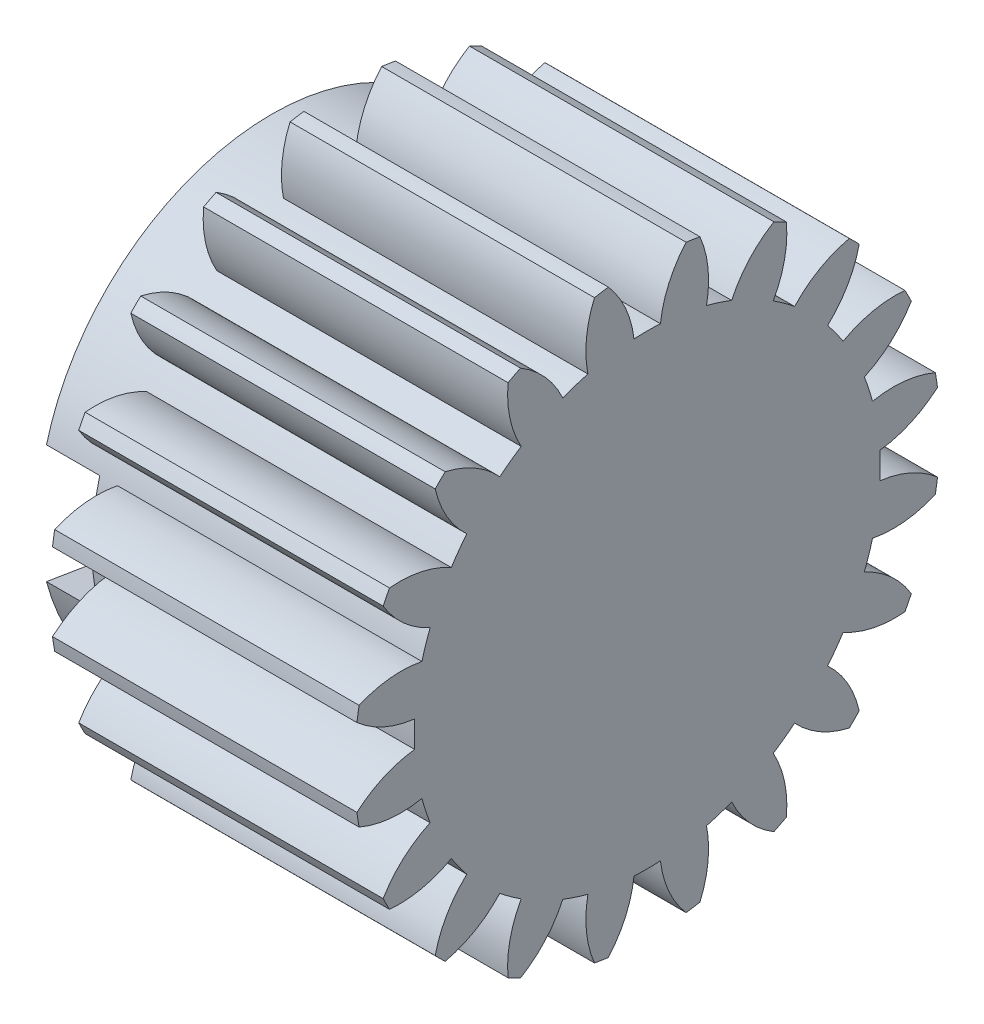
SolidWorks part; units mm, degrees
ref_plane "Plane1" through (0, 0, 0) normal (0, 0, 1) x (1, 0, 0)
ref_plane "Plane2" through (0, 0, 0) normal (0, 1, 0) x (1, 0, 0)
ref_plane "Plane3" through (0, 0, 0) normal (1, 0, 0) x (0, 0, -1)
other "Configuration Table"
sketch "HoldingSke" plane through (0, 0, 0) normal (0, 1, 0) x (1, 0, 0)
  line L0 (0, 0) -> (0.6265, -0.228)
  line L1 (-15, 0) -> (100, 0) construction
  line L2 (0, 0) -> (-2.1039, 2.3779)
  line L3 (0, 0) -> (-11.863, 4.5341)
  line L4 (0, 0) -> (8.1152, 2.9537)
  line L5 (0, 0) -> (-14.9912, -5.5913)
  line L6 (0, 0) -> (-8.2896, -5.593)
  line L7 (-2.1039, 2.3779) -> (1.3401, 18.0029)
  line L8 (-76.2, 54.61) -> (-76.1, 54.61)
  line L9 (-71.009, 38.7566) -> (-53.1078, 45.2721)
  line L10 (-76.2, 71.12) -> (104.1128, 71.12)
  line L11 (0, 0) -> (-10, 0)
  line L12 (-76.2, 101.6) -> (-76.147, 101.6)
  line L13 (24.9733, 27.94) -> (52.9518, 28.4284)
  line L14 (24.9733, 27.94) -> (24.9743, 27.94)
  line L15 (24.9733, 27.94) -> (100.4006, 29.5858)
  line L16 (-63.627, -1.5) -> (-12.827, -1.5)
  circle A0 centre (0, 0) radius 0.4
  circle A1 centre (0, 0) radius 13.124
  circle A2 centre (0, 0) radius 25
  circle A3 centre (0, 0) radius 0.4
  dimension "Num_teeth" = 20
  dimension "Pitch_radius" = 180.3128
  dimension "Width" = 10
  dimension "Thickness" = 10
sketch "BasProSke" plane through (0, 0, 0) normal (0, 1, 0) x (1, 0, 0)
  line L0 (-10, 0) -> (60, 0) construction
  line L1 (0, 0) -> (0, 16.5)
  line L2 (0, 0) -> (10, 0)
  line L3 (10, 0) -> (10, 16.5)
  line L4 (10, 16.5) -> (0, 16.5)
  dimension "Thickness" = 10
  dimension "Diameter" = 33
revolve "Base-Revolve" add sketch "BasProSke" angle 360 about L0
sketch "TooCutSke" plane through (0, 0, 0) normal (1, 0, 0) x (0, 0, -1)
  line L1 (0, 0) -> (0, 107) construction
  line L2 (0, 0) -> (-1.2696, 14.9462) construction
  line L3 (0, 0) -> (-4.6808, 29.5532) construction
  line L4 (-1.2696, 14.9462) -> (-2.3404, 14.7766) construction
  arc A0 (0.7438, 13.1029) -> (-0.7438, 13.1029) centre (0, 0) ccw
  arc A1 (2.21, 16.377) -> (-2.21, 16.377) centre (0, 0) ccw
  circle A2 centre (0, 0) radius 15 construction
  circle A3 centre (0, 0) radius 14.0954 construction
  arc A4 (-0.7438, 13.1029) -> (-2.21, 16.377) centre (-6.7025, 12.3999) ccw
  arc A5 (2.21, 16.377) -> (0.7438, 13.1029) centre (6.7025, 12.3999) ccw
extrude "ToothCut" cut sketch "TooCutSke" along normal through all
fillet "Breaks" [suppressed] radius 0.03 tangent propagation no
fillet "RootFillets" [suppressed] radius 0.376
pattern_circular "TeethCuts" count 20 every 18 about axis through (-10, 0, 0) along (1, 0, 0) of "ToothCut", "RootFillets", "Breaks"
sketch "HubNeaOneSke" plane through (0, 0, 0) normal (-1, 0, 0) x (0, 0, 1)
  circle A0 centre (0, 0) radius 13.124
  dimension "Diameter" = 26.248
extrude "HubNearOne" add sketch "HubNeaOneSke" along normal blind 6.0001
sketch "HubNeaBotSke" plane through (0, 0, 0) normal (-1, 0, 0) x (0, 0, 1)
  circle A0 centre (0, 0) radius 13.124
  dimension "Diameter" = 26.248
extrude "HubNearBoth" [suppressed] add sketch "HubNeaBotSke" along normal blind 3
ref_plane "FarPln" through (10, 0, 0) normal (1, 0, 0) x (0, 0, -1)
sketch "HubFarSke" plane through (10, 0, 0) normal (1, 0, 0) x (0, 0, -1)
  circle A0 centre (0, 0) radius 13.124
  dimension "Diameter" = 26.248
extrude "HubFar" [suppressed] add sketch "HubFarSke" along normal blind 3
sketch "BorSke" plane through (0, 0, 0) normal (1, 0, 0) x (0, 0, -1)
  circle A0 centre (0, 0) radius 0.4
  dimension "Diameter" = 0.8
extrude "Bore" cut sketch "BorSke" along normal mid plane 32.0001
sketch "KeySke" plane through (0, 0, 0) normal (1, 0, 0) x (0, 0, -1)
  line L0 (-0.05, 0) -> (-0.05, 0.5)
  line L1 (-0.05, 0.5) -> (0.05, 0.5)
  line L2 (0.05, 0.5) -> (0.05, 0)
  line L3 (0, 0) -> (0, 34) construction
  line L4 (-0.05, 0) -> (0.05, 0)
  dimension "Width" = 0.1
extrude "Keyway" [suppressed] cut sketch "KeySke" along normal mid plane 32.0001
pattern_circular "Keyway2" [suppressed] count 2 every 90 about axis through (-10, 0, 0) along (1, 0, 0) reverse direction yes
sketch "Sketch1" plane through (-6.0001, 0, 0) normal (-1, 0, 0) x (0, 0, 1)
  line L0 (0, 0) -> (31.5508, 0) construction
  line L1 (15.95, 2.8) -> (4.4173, 4.7)
  line L2 (15.95, -2.8) -> (4.4173, -4.7)
  line L3 (0, 10.0438) -> (0, -22.686) construction
  line L4 (-15.95, -2.8) -> (-4.4173, -4.7)
  line L5 (-15.95, 2.8) -> (-4.4173, 4.7)
  arc A0 (4.4173, 4.7) -> (-4.4173, 4.7) centre (0, 0) ccw
  circle A1 centre (0, 0) radius 4.25 construction
  arc A2 (15.95, -2.8) -> (15.95, 2.8) centre (15.95, 0) ccw
  arc A3 (-15.95, -2.8) -> (-15.95, 2.8) centre (-15.95, 0) cw
  arc A4 (-4.4173, -4.7) -> (4.4173, -4.7) centre (0, 0) ccw
  point P6 (4.25, 0)
  point P7 (18.75, 0)
  point P8 (4.4173, 4.7)
  point P9 (4.4173, -4.7)
  dimension "D1" = 8.5
  dimension "12.5" = 12.9
  dimension "D2" = 5.6
  dimension "D3" = 14.5
  dimension "D4" = 9.4
extrude "Cut-Extrude1" cut sketch "Sketch1" against normal blind 5
sketch "Sketch2" plane through (10, 0, 0) normal (1, 0, 0) x (0, 0, -1)
  arc A80 (-16.354, 2.1898) -> (-13.1029, 0.7438) centre (-12.3999, 6.7025) ccw
  arc A81 (-13.1029, 0.7438) -> (-13.1029, -0.7438) centre (0, 0) ccw
  arc A82 (-13.1029, -0.7438) -> (-16.354, -2.1898) centre (-12.3999, -6.7025) ccw
  arc A83 (-16.354, -2.1898) -> (-16.2303, -2.9711) centre (0, 0) ccw
  arc A84 (-16.2303, -2.9711) -> (-12.6915, -3.3416) centre (-13.8642, 2.5427) ccw
  arc A85 (-12.6915, -3.3416) -> (-12.2318, -4.7564) centre (0, 0) ccw
  arc A86 (-12.2318, -4.7564) -> (-14.8769, -7.1363) centre (-9.7218, -10.2062) ccw
  arc A87 (-14.8769, -7.1363) -> (-14.5178, -7.8411) centre (0, 0) ccw
  arc A88 (-14.5178, -7.8411) -> (-11.0377, -7.0999) centre (-13.9713, -1.866) ccw
  arc A89 (-11.0377, -7.0999) -> (-10.1633, -8.3035) centre (0, 0) ccw
  arc A90 (-10.1633, -8.3035) -> (-11.9436, -11.3842) centre (-6.0921, -12.7109) ccw
  arc A91 (-11.9436, -11.3842) -> (-11.3842, -11.9436) centre (0, 0) ccw
  arc A92 (-11.3842, -11.9436) -> (-8.3035, -10.1633) centre (-12.7109, -6.0921) ccw
  arc A93 (-8.3035, -10.1633) -> (-7.0999, -11.0377) centre (0, 0) ccw
  arc A94 (-7.0999, -11.0377) -> (-7.8411, -14.5178) centre (-1.866, -13.9713) ccw
  arc A95 (-7.8411, -14.5178) -> (-7.1363, -14.8769) centre (0, 0) ccw
  arc A96 (-7.1363, -14.8769) -> (-4.7564, -12.2318) centre (-10.2062, -9.7218) ccw
  arc A97 (-4.7564, -12.2318) -> (-3.3416, -12.6915) centre (0, 0) ccw
  arc A98 (-3.3416, -12.6915) -> (-2.9711, -16.2303) centre (2.5427, -13.8642) ccw
  arc A99 (-2.9711, -16.2303) -> (-2.1898, -16.354) centre (0, 0) ccw
  arc A100 (-2.1898, -16.354) -> (-0.7438, -13.1029) centre (-6.7025, -12.3999) ccw
  arc A101 (-0.7438, -13.1029) -> (0.7438, -13.1029) centre (0, 0) ccw
  arc A102 (0.7438, -13.1029) -> (2.1898, -16.354) centre (6.7025, -12.3999) ccw
  arc A103 (2.1898, -16.354) -> (2.9711, -16.2303) centre (0, 0) ccw
  arc A104 (2.9711, -16.2303) -> (3.3416, -12.6915) centre (-2.5427, -13.8642) ccw
  arc A105 (3.3416, -12.6915) -> (4.7564, -12.2318) centre (0, 0) ccw
  arc A106 (4.7564, -12.2318) -> (7.1363, -14.8769) centre (10.2062, -9.7218) ccw
  arc A107 (7.1363, -14.8769) -> (7.8411, -14.5178) centre (0, 0) ccw
  arc A108 (7.8411, -14.5178) -> (7.0999, -11.0377) centre (1.866, -13.9713) ccw
  arc A109 (7.0999, -11.0377) -> (8.3035, -10.1633) centre (0, 0) ccw
  arc A110 (8.3035, -10.1633) -> (11.3842, -11.9436) centre (12.7109, -6.0921) ccw
  arc A111 (11.3842, -11.9436) -> (11.9436, -11.3842) centre (0, 0) ccw
  arc A112 (11.9436, -11.3842) -> (10.1633, -8.3035) centre (6.0921, -12.7109) ccw
  arc A113 (10.1633, -8.3035) -> (11.0377, -7.0999) centre (0, 0) ccw
  arc A114 (11.0377, -7.0999) -> (14.5178, -7.8411) centre (13.9713, -1.866) ccw
  arc A115 (14.5178, -7.8411) -> (14.8769, -7.1363) centre (0, 0) ccw
  arc A116 (14.8769, -7.1363) -> (12.2318, -4.7564) centre (9.7218, -10.2062) ccw
  arc A117 (12.2318, -4.7564) -> (12.6915, -3.3416) centre (0, 0) ccw
  arc A118 (12.6915, -3.3416) -> (16.2303, -2.9711) centre (13.8642, 2.5427) ccw
  arc A119 (16.2303, -2.9711) -> (16.354, -2.1898) centre (0, 0) ccw
  arc A120 (16.354, -2.1898) -> (13.1029, -0.7438) centre (12.3999, -6.7025) ccw
  arc A121 (13.1029, -0.7438) -> (13.1029, 0.7438) centre (0, 0) ccw
  arc A122 (13.1029, 0.7438) -> (16.354, 2.1898) centre (12.3999, 6.7025) ccw
  arc A123 (16.354, 2.1898) -> (16.2303, 2.9711) centre (0, 0) ccw
  arc A124 (16.2303, 2.9711) -> (12.6915, 3.3416) centre (13.8642, -2.5427) ccw
  arc A125 (12.6915, 3.3416) -> (12.2318, 4.7564) centre (0, 0) ccw
  arc A126 (12.2318, 4.7564) -> (14.8769, 7.1363) centre (9.7218, 10.2062) ccw
  arc A127 (14.8769, 7.1363) -> (14.5178, 7.8411) centre (0, 0) ccw
  arc A128 (14.5178, 7.8411) -> (11.0377, 7.0999) centre (13.9713, 1.866) ccw
  arc A129 (11.0377, 7.0999) -> (10.1633, 8.3035) centre (0, 0) ccw
  arc A130 (10.1633, 8.3035) -> (11.9436, 11.3842) centre (6.0921, 12.7109) ccw
  arc A131 (11.9436, 11.3842) -> (11.3842, 11.9436) centre (0, 0) ccw
  arc A132 (11.3842, 11.9436) -> (8.3035, 10.1633) centre (12.7109, 6.0921) ccw
  arc A133 (8.3035, 10.1633) -> (7.0999, 11.0377) centre (0, 0) ccw
  arc A134 (7.0999, 11.0377) -> (7.8411, 14.5178) centre (1.866, 13.9713) ccw
  arc A135 (7.8411, 14.5178) -> (7.1363, 14.8769) centre (0, 0) ccw
  arc A136 (7.1363, 14.8769) -> (4.7564, 12.2318) centre (10.2062, 9.7218) ccw
  arc A137 (4.7564, 12.2318) -> (3.3416, 12.6915) centre (0, 0) ccw
  arc A138 (3.3416, 12.6915) -> (2.9711, 16.2303) centre (-2.5427, 13.8642) ccw
  arc A139 (2.9711, 16.2303) -> (2.1898, 16.354) centre (0, 0) ccw
  arc A140 (2.1898, 16.354) -> (0.7438, 13.1029) centre (6.7025, 12.3999) ccw
  arc A141 (0.7438, 13.1029) -> (-0.7438, 13.1029) centre (0, 0) ccw
  arc A142 (-0.7438, 13.1029) -> (-2.1898, 16.354) centre (-6.7025, 12.3999) ccw
  arc A143 (-2.1898, 16.354) -> (-2.9711, 16.2303) centre (0, 0) ccw
  arc A144 (-2.9711, 16.2303) -> (-3.3416, 12.6915) centre (2.5427, 13.8642) ccw
  arc A145 (-3.3416, 12.6915) -> (-4.7564, 12.2318) centre (0, 0) ccw
  arc A146 (-4.7564, 12.2318) -> (-7.1363, 14.8769) centre (-10.2062, 9.7218) ccw
  arc A147 (-7.1363, 14.8769) -> (-7.8411, 14.5178) centre (0, 0) ccw
  arc A148 (-7.8411, 14.5178) -> (-7.0999, 11.0377) centre (-1.866, 13.9713) ccw
  arc A149 (-7.0999, 11.0377) -> (-8.3035, 10.1633) centre (0, 0) ccw
  arc A150 (-8.3035, 10.1633) -> (-11.3842, 11.9436) centre (-12.7109, 6.0921) ccw
  arc A151 (-11.3842, 11.9436) -> (-11.9436, 11.3842) centre (0, 0) ccw
  arc A152 (-11.9436, 11.3842) -> (-10.1633, 8.3035) centre (-6.0921, 12.7109) ccw
  arc A153 (-10.1633, 8.3035) -> (-11.0377, 7.0999) centre (0, 0) ccw
  arc A154 (-11.0377, 7.0999) -> (-14.5178, 7.8411) centre (-13.9713, 1.866) ccw
  arc A155 (-14.5178, 7.8411) -> (-14.8769, 7.1363) centre (0, 0) ccw
  arc A156 (-14.8769, 7.1363) -> (-12.2318, 4.7564) centre (-9.7218, 10.2062) ccw
  arc A157 (-12.2318, 4.7564) -> (-12.6915, 3.3416) centre (0, 0) ccw
  arc A158 (-12.6915, 3.3416) -> (-16.2303, 2.9711) centre (-13.8642, -2.5427) ccw
  arc A159 (-16.2303, 2.9711) -> (-16.354, 2.1898) centre (0, 0) ccw
  arc A160 (-16.354, 2.1898) -> (-13.1029, 0.7438) centre (-12.3999, 6.7025) ccw
  arc A161 (-13.1029, 0.7438) -> (-13.1029, -0.7438) centre (0, 0) ccw
  arc A162 (-13.1029, -0.7438) -> (-16.354, -2.1898) centre (-12.3999, -6.7025) ccw
  arc A163 (-16.354, -2.1898) -> (-16.2303, -2.9711) centre (0, 0) ccw
  arc A164 (-16.2303, -2.9711) -> (-12.6915, -3.3416) centre (-13.8642, 2.5427) ccw
  arc A165 (-12.6915, -3.3416) -> (-12.2318, -4.7564) centre (0, 0) ccw
  arc A166 (-12.2318, -4.7564) -> (-14.8769, -7.1363) centre (-9.7218, -10.2062) ccw
  arc A167 (-14.8769, -7.1363) -> (-14.5178, -7.8411) centre (0, 0) ccw
  arc A168 (-14.5178, -7.8411) -> (-11.0377, -7.0999) centre (-13.9713, -1.866) ccw
  arc A169 (-11.0377, -7.0999) -> (-10.1633, -8.3035) centre (0, 0) ccw
  arc A170 (-10.1633, -8.3035) -> (-11.9436, -11.3842) centre (-6.0921, -12.7109) ccw
  arc A171 (-11.9436, -11.3842) -> (-11.3842, -11.9436) centre (0, 0) ccw
  arc A172 (-11.3842, -11.9436) -> (-8.3035, -10.1633) centre (-12.7109, -6.0921) ccw
  arc A173 (-8.3035, -10.1633) -> (-7.0999, -11.0377) centre (0, 0) ccw
  arc A174 (-7.0999, -11.0377) -> (-7.8411, -14.5178) centre (-1.866, -13.9713) ccw
  arc A175 (-7.8411, -14.5178) -> (-7.1363, -14.8769) centre (0, 0) ccw
  arc A176 (-7.1363, -14.8769) -> (-4.7564, -12.2318) centre (-10.2062, -9.7218) ccw
  arc A177 (-4.7564, -12.2318) -> (-3.3416, -12.6915) centre (0, 0) ccw
  arc A178 (-3.3416, -12.6915) -> (-2.9711, -16.2303) centre (2.5427, -13.8642) ccw
  arc A179 (-2.9711, -16.2303) -> (-2.1898, -16.354) centre (0, 0) ccw
  arc A180 (-2.1898, -16.354) -> (-0.7438, -13.1029) centre (-6.7025, -12.3999) ccw
  arc A181 (-0.7438, -13.1029) -> (0.7438, -13.1029) centre (0, 0) ccw
  arc A182 (0.7438, -13.1029) -> (2.1898, -16.354) centre (6.7025, -12.3999) ccw
  arc A183 (2.1898, -16.354) -> (2.9711, -16.2303) centre (0, 0) ccw
  arc A184 (2.9711, -16.2303) -> (3.3416, -12.6915) centre (-2.5427, -13.8642) ccw
  arc A185 (3.3416, -12.6915) -> (4.7564, -12.2318) centre (0, 0) ccw
  arc A186 (4.7564, -12.2318) -> (7.1363, -14.8769) centre (10.2062, -9.7218) ccw
  arc A187 (7.1363, -14.8769) -> (7.8411, -14.5178) centre (0, 0) ccw
  arc A188 (7.8411, -14.5178) -> (7.0999, -11.0377) centre (1.866, -13.9713) ccw
  arc A189 (7.0999, -11.0377) -> (8.3035, -10.1633) centre (0, 0) ccw
  arc A190 (8.3035, -10.1633) -> (11.3842, -11.9436) centre (12.7109, -6.0921) ccw
  arc A191 (11.3842, -11.9436) -> (11.9436, -11.3842) centre (0, 0) ccw
  arc A192 (11.9436, -11.3842) -> (10.1633, -8.3035) centre (6.0921, -12.7109) ccw
  arc A193 (10.1633, -8.3035) -> (11.0377, -7.0999) centre (0, 0) ccw
  arc A194 (11.0377, -7.0999) -> (14.5178, -7.8411) centre (13.9713, -1.866) ccw
  arc A195 (14.5178, -7.8411) -> (14.8769, -7.1363) centre (0, 0) ccw
  arc A196 (14.8769, -7.1363) -> (12.2318, -4.7564) centre (9.7218, -10.2062) ccw
  arc A197 (12.2318, -4.7564) -> (12.6915, -3.3416) centre (0, 0) ccw
  arc A198 (12.6915, -3.3416) -> (16.2303, -2.9711) centre (13.8642, 2.5427) ccw
  arc A199 (16.2303, -2.9711) -> (16.354, -2.1898) centre (0, 0) ccw
  arc A200 (16.354, -2.1898) -> (13.1029, -0.7438) centre (12.3999, -6.7025) ccw
  arc A201 (13.1029, -0.7438) -> (13.1029, 0.7438) centre (0, 0) ccw
  arc A202 (13.1029, 0.7438) -> (16.354, 2.1898) centre (12.3999, 6.7025) ccw
  arc A203 (16.354, 2.1898) -> (16.2303, 2.9711) centre (0, 0) ccw
  arc A204 (16.2303, 2.9711) -> (12.6915, 3.3416) centre (13.8642, -2.5427) ccw
  arc A205 (12.6915, 3.3416) -> (12.2318, 4.7564) centre (0, 0) ccw
  arc A206 (12.2318, 4.7564) -> (14.8769, 7.1363) centre (9.7218, 10.2062) ccw
  arc A207 (14.8769, 7.1363) -> (14.5178, 7.8411) centre (0, 0) ccw
  arc A208 (14.5178, 7.8411) -> (11.0377, 7.0999) centre (13.9713, 1.866) ccw
  arc A209 (11.0377, 7.0999) -> (10.1633, 8.3035) centre (0, 0) ccw
  arc A210 (10.1633, 8.3035) -> (11.9436, 11.3842) centre (6.0921, 12.7109) ccw
  arc A211 (11.9436, 11.3842) -> (11.3842, 11.9436) centre (0, 0) ccw
  arc A212 (11.3842, 11.9436) -> (8.3035, 10.1633) centre (12.7109, 6.0921) ccw
  arc A213 (8.3035, 10.1633) -> (7.0999, 11.0377) centre (0, 0) ccw
  arc A214 (7.0999, 11.0377) -> (7.8411, 14.5178) centre (1.866, 13.9713) ccw
  arc A215 (7.8411, 14.5178) -> (7.1363, 14.8769) centre (0, 0) ccw
  arc A216 (7.1363, 14.8769) -> (4.7564, 12.2318) centre (10.2062, 9.7218) ccw
  arc A217 (4.7564, 12.2318) -> (3.3416, 12.6915) centre (0, 0) ccw
  arc A218 (3.3416, 12.6915) -> (2.9711, 16.2303) centre (-2.5427, 13.8642) ccw
  arc A219 (2.9711, 16.2303) -> (2.1898, 16.354) centre (0, 0) ccw
  arc A220 (2.1898, 16.354) -> (0.7438, 13.1029) centre (6.7025, 12.3999) ccw
  arc A221 (0.7438, 13.1029) -> (-0.7438, 13.1029) centre (0, 0) ccw
  arc A222 (-0.7438, 13.1029) -> (-2.1898, 16.354) centre (-6.7025, 12.3999) ccw
  arc A223 (-2.1898, 16.354) -> (-2.9711, 16.2303) centre (0, 0) ccw
  arc A224 (-2.9711, 16.2303) -> (-3.3416, 12.6915) centre (2.5427, 13.8642) ccw
  arc A225 (-3.3416, 12.6915) -> (-4.7564, 12.2318) centre (0, 0) ccw
  arc A226 (-4.7564, 12.2318) -> (-7.1363, 14.8769) centre (-10.2062, 9.7218) ccw
  arc A227 (-7.1363, 14.8769) -> (-7.8411, 14.5178) centre (0, 0) ccw
  arc A228 (-7.8411, 14.5178) -> (-7.0999, 11.0377) centre (-1.866, 13.9713) ccw
  arc A229 (-7.0999, 11.0377) -> (-8.3035, 10.1633) centre (0, 0) ccw
  arc A230 (-8.3035, 10.1633) -> (-11.3842, 11.9436) centre (-12.7109, 6.0921) ccw
  arc A231 (-11.3842, 11.9436) -> (-11.9436, 11.3842) centre (0, 0) ccw
  arc A232 (-11.9436, 11.3842) -> (-10.1633, 8.3035) centre (-6.0921, 12.7109) ccw
  arc A233 (-10.1633, 8.3035) -> (-11.0377, 7.0999) centre (0, 0) ccw
  arc A234 (-11.0377, 7.0999) -> (-14.5178, 7.8411) centre (-13.9713, 1.866) ccw
  arc A235 (-14.5178, 7.8411) -> (-14.8769, 7.1363) centre (0, 0) ccw
  arc A236 (-14.8769, 7.1363) -> (-12.2318, 4.7564) centre (-9.7218, 10.2062) ccw
  arc A237 (-12.2318, 4.7564) -> (-12.6915, 3.3416) centre (0, 0) ccw
  arc A238 (-12.6915, 3.3416) -> (-16.2303, 2.9711) centre (-13.8642, -2.5427) ccw
  arc A239 (-16.2303, 2.9711) -> (-16.354, 2.1898) centre (0, 0) ccw
  dimension "D1" = 0
extrude "Boss-Extrude1" add sketch "Sketch2" along normal blind 7.15 contours A160 A161 A162 A163 A164 A165 A166 A167 A168 A169 A170 A171 A172 A173 A174 A175 A176 A177 A178 A179 A180 A181 A182 A183 A184 A185 A186 A187 A188 A189 A190 A191 A192 A193 A194 A195 A196 A197 A198 A199 A200 A201 A202 A203 A204 A205 A206 A207 A208 A209 A210 A211 A212 A213 A214 A215 A216 A217 A218 A219 A220 A221 A222 A223 A224 A225 A226 A227 A228 A229 A230 A231 A232 A233 A234 A235 A236 A237 A238 A239
sketch "Sketch4" plane through (-6.0001, 0, 0) normal (-1, 0, 0) x (0, 0, 1)
  circle A0 centre (0, 0) radius 13.124
extrude "Cut-Extrude2" cut sketch "Sketch4" against normal blind 2
sketch "Sketch5" plane through (17.15, 0, 0) normal (1, 0, 0) x (0, 0, -1)
  arc A80 (-16.2303, 2.9711) -> (-16.354, 2.1898) centre (0, 0) ccw
  arc A81 (-16.354, 2.1898) -> (-13.1029, 0.7438) centre (-12.3999, 6.7025) ccw
  arc A82 (-13.1029, 0.7438) -> (-13.1029, -0.7438) centre (0, 0) ccw
  arc A83 (-13.1029, -0.7438) -> (-16.354, -2.1898) centre (-12.3999, -6.7025) ccw
  arc A84 (-16.354, -2.1898) -> (-16.2303, -2.9711) centre (0, 0) ccw
  arc A85 (-16.2303, -2.9711) -> (-12.6915, -3.3416) centre (-13.8642, 2.5427) ccw
  arc A86 (-12.6915, -3.3416) -> (-12.2318, -4.7564) centre (0, 0) ccw
  arc A87 (-12.2318, -4.7564) -> (-14.8769, -7.1363) centre (-9.7218, -10.2062) ccw
  arc A88 (-14.8769, -7.1363) -> (-14.5178, -7.8411) centre (0, 0) ccw
  arc A89 (-14.5178, -7.8411) -> (-11.0377, -7.0999) centre (-13.9713, -1.866) ccw
  arc A90 (-11.0377, -7.0999) -> (-10.1633, -8.3035) centre (0, 0) ccw
  arc A91 (-10.1633, -8.3035) -> (-11.9436, -11.3842) centre (-6.0921, -12.7109) ccw
  arc A92 (-11.9436, -11.3842) -> (-11.3842, -11.9436) centre (0, 0) ccw
  arc A93 (-11.3842, -11.9436) -> (-8.3035, -10.1633) centre (-12.7109, -6.0921) ccw
  arc A94 (-8.3035, -10.1633) -> (-7.0999, -11.0377) centre (0, 0) ccw
  arc A95 (-7.0999, -11.0377) -> (-7.8411, -14.5178) centre (-1.866, -13.9713) ccw
  arc A96 (-7.8411, -14.5178) -> (-7.1363, -14.8769) centre (0, 0) ccw
  arc A97 (-7.1363, -14.8769) -> (-4.7564, -12.2318) centre (-10.2062, -9.7218) ccw
  arc A98 (-4.7564, -12.2318) -> (-3.3416, -12.6915) centre (0, 0) ccw
  arc A99 (-3.3416, -12.6915) -> (-2.9711, -16.2303) centre (2.5427, -13.8642) ccw
  arc A100 (-2.9711, -16.2303) -> (-2.1898, -16.354) centre (0, 0) ccw
  arc A101 (-2.1898, -16.354) -> (-0.7438, -13.1029) centre (-6.7025, -12.3999) ccw
  arc A102 (-0.7438, -13.1029) -> (0.7438, -13.1029) centre (0, 0) ccw
  arc A103 (0.7438, -13.1029) -> (2.1898, -16.354) centre (6.7025, -12.3999) ccw
  arc A104 (2.1898, -16.354) -> (2.9711, -16.2303) centre (0, 0) ccw
  arc A105 (2.9711, -16.2303) -> (3.3416, -12.6915) centre (-2.5427, -13.8642) ccw
  arc A106 (3.3416, -12.6915) -> (4.7564, -12.2318) centre (0, 0) ccw
  arc A107 (4.7564, -12.2318) -> (7.1363, -14.8769) centre (10.2062, -9.7218) ccw
  arc A108 (7.1363, -14.8769) -> (7.8411, -14.5178) centre (0, 0) ccw
  arc A109 (7.8411, -14.5178) -> (7.0999, -11.0377) centre (1.866, -13.9713) ccw
  arc A110 (7.0999, -11.0377) -> (8.3035, -10.1633) centre (0, 0) ccw
  arc A111 (8.3035, -10.1633) -> (11.3842, -11.9436) centre (12.7109, -6.0921) ccw
  arc A112 (11.3842, -11.9436) -> (11.9436, -11.3842) centre (0, 0) ccw
  arc A113 (11.9436, -11.3842) -> (10.1633, -8.3035) centre (6.0921, -12.7109) ccw
  arc A114 (10.1633, -8.3035) -> (11.0377, -7.0999) centre (0, 0) ccw
  arc A115 (11.0377, -7.0999) -> (14.5178, -7.8411) centre (13.9713, -1.866) ccw
  arc A116 (14.5178, -7.8411) -> (14.8769, -7.1363) centre (0, 0) ccw
  arc A117 (14.8769, -7.1363) -> (12.2318, -4.7564) centre (9.7218, -10.2062) ccw
  arc A118 (12.2318, -4.7564) -> (12.6915, -3.3416) centre (0, 0) ccw
  arc A119 (12.6915, -3.3416) -> (16.2303, -2.9711) centre (13.8642, 2.5427) ccw
  arc A120 (16.2303, -2.9711) -> (16.354, -2.1898) centre (0, 0) ccw
  arc A121 (16.354, -2.1898) -> (13.1029, -0.7438) centre (12.3999, -6.7025) ccw
  arc A122 (13.1029, -0.7438) -> (13.1029, 0.7438) centre (0, 0) ccw
  arc A123 (13.1029, 0.7438) -> (16.354, 2.1898) centre (12.3999, 6.7025) ccw
  arc A124 (16.354, 2.1898) -> (16.2303, 2.9711) centre (0, 0) ccw
  arc A125 (16.2303, 2.9711) -> (12.6915, 3.3416) centre (13.8642, -2.5427) ccw
  arc A126 (12.6915, 3.3416) -> (12.2318, 4.7564) centre (0, 0) ccw
  arc A127 (12.2318, 4.7564) -> (14.8769, 7.1363) centre (9.7218, 10.2062) ccw
  arc A128 (14.8769, 7.1363) -> (14.5178, 7.8411) centre (0, 0) ccw
  arc A129 (14.5178, 7.8411) -> (11.0377, 7.0999) centre (13.9713, 1.866) ccw
  arc A130 (11.0377, 7.0999) -> (10.1633, 8.3035) centre (0, 0) ccw
  arc A131 (10.1633, 8.3035) -> (11.9436, 11.3842) centre (6.0921, 12.7109) ccw
  arc A132 (11.9436, 11.3842) -> (11.3842, 11.9436) centre (0, 0) ccw
  arc A133 (11.3842, 11.9436) -> (8.3035, 10.1633) centre (12.7109, 6.0921) ccw
  arc A134 (8.3035, 10.1633) -> (7.0999, 11.0377) centre (0, 0) ccw
  arc A135 (7.0999, 11.0377) -> (7.8411, 14.5178) centre (1.866, 13.9713) ccw
  arc A136 (7.8411, 14.5178) -> (7.1363, 14.8769) centre (0, 0) ccw
  arc A137 (7.1363, 14.8769) -> (4.7564, 12.2318) centre (10.2062, 9.7218) ccw
  arc A138 (4.7564, 12.2318) -> (3.3416, 12.6915) centre (0, 0) ccw
  arc A139 (3.3416, 12.6915) -> (2.9711, 16.2303) centre (-2.5427, 13.8642) ccw
  arc A140 (2.9711, 16.2303) -> (2.1898, 16.354) centre (0, 0) ccw
  arc A141 (2.1898, 16.354) -> (0.7438, 13.1029) centre (6.7025, 12.3999) ccw
  arc A142 (0.7438, 13.1029) -> (-0.7438, 13.1029) centre (0, 0) ccw
  arc A143 (-0.7438, 13.1029) -> (-2.1898, 16.354) centre (-6.7025, 12.3999) ccw
  arc A144 (-2.1898, 16.354) -> (-2.9711, 16.2303) centre (0, 0) ccw
  arc A145 (-2.9711, 16.2303) -> (-3.3416, 12.6915) centre (2.5427, 13.8642) ccw
  arc A146 (-3.3416, 12.6915) -> (-4.7564, 12.2318) centre (0, 0) ccw
  arc A147 (-4.7564, 12.2318) -> (-7.1363, 14.8769) centre (-10.2062, 9.7218) ccw
  arc A148 (-7.1363, 14.8769) -> (-7.8411, 14.5178) centre (0, 0) ccw
  arc A149 (-7.8411, 14.5178) -> (-7.0999, 11.0377) centre (-1.866, 13.9713) ccw
  arc A150 (-7.0999, 11.0377) -> (-8.3035, 10.1633) centre (0, 0) ccw
  arc A151 (-8.3035, 10.1633) -> (-11.3842, 11.9436) centre (-12.7109, 6.0921) ccw
  arc A152 (-11.3842, 11.9436) -> (-11.9436, 11.3842) centre (0, 0) ccw
  arc A153 (-11.9436, 11.3842) -> (-10.1633, 8.3035) centre (-6.0921, 12.7109) ccw
  arc A154 (-10.1633, 8.3035) -> (-11.0377, 7.0999) centre (0, 0) ccw
  arc A155 (-11.0377, 7.0999) -> (-14.5178, 7.8411) centre (-13.9713, 1.866) ccw
  arc A156 (-14.5178, 7.8411) -> (-14.8769, 7.1363) centre (0, 0) ccw
  arc A157 (-14.8769, 7.1363) -> (-12.2318, 4.7564) centre (-9.7218, 10.2062) ccw
  arc A158 (-12.2318, 4.7564) -> (-12.6915, 3.3416) centre (0, 0) ccw
  arc A159 (-12.6915, 3.3416) -> (-16.2303, 2.9711) centre (-13.8642, -2.5427) ccw
  arc A160 (-16.2303, 2.9711) -> (-16.354, 2.1898) centre (0, 0) ccw
  arc A161 (-16.354, 2.1898) -> (-13.1029, 0.7438) centre (-12.3999, 6.7025) ccw
  arc A162 (-13.1029, 0.7438) -> (-13.1029, -0.7438) centre (0, 0) ccw
  arc A163 (-13.1029, -0.7438) -> (-16.354, -2.1898) centre (-12.3999, -6.7025) ccw
  arc A164 (-16.354, -2.1898) -> (-16.2303, -2.9711) centre (0, 0) ccw
  arc A165 (-16.2303, -2.9711) -> (-12.6915, -3.3416) centre (-13.8642, 2.5427) ccw
  arc A166 (-12.6915, -3.3416) -> (-12.2318, -4.7564) centre (0, 0) ccw
  arc A167 (-12.2318, -4.7564) -> (-14.8769, -7.1363) centre (-9.7218, -10.2062) ccw
  arc A168 (-14.8769, -7.1363) -> (-14.5178, -7.8411) centre (0, 0) ccw
  arc A169 (-14.5178, -7.8411) -> (-11.0377, -7.0999) centre (-13.9713, -1.866) ccw
  arc A170 (-11.0377, -7.0999) -> (-10.1633, -8.3035) centre (0, 0) ccw
  arc A171 (-10.1633, -8.3035) -> (-11.9436, -11.3842) centre (-6.0921, -12.7109) ccw
  arc A172 (-11.9436, -11.3842) -> (-11.3842, -11.9436) centre (0, 0) ccw
  arc A173 (-11.3842, -11.9436) -> (-8.3035, -10.1633) centre (-12.7109, -6.0921) ccw
  arc A174 (-8.3035, -10.1633) -> (-7.0999, -11.0377) centre (0, 0) ccw
  arc A175 (-7.0999, -11.0377) -> (-7.8411, -14.5178) centre (-1.866, -13.9713) ccw
  arc A176 (-7.8411, -14.5178) -> (-7.1363, -14.8769) centre (0, 0) ccw
  arc A177 (-7.1363, -14.8769) -> (-4.7564, -12.2318) centre (-10.2062, -9.7218) ccw
  arc A178 (-4.7564, -12.2318) -> (-3.3416, -12.6915) centre (0, 0) ccw
  arc A179 (-3.3416, -12.6915) -> (-2.9711, -16.2303) centre (2.5427, -13.8642) ccw
  arc A180 (-2.9711, -16.2303) -> (-2.1898, -16.354) centre (0, 0) ccw
  arc A181 (-2.1898, -16.354) -> (-0.7438, -13.1029) centre (-6.7025, -12.3999) ccw
  arc A182 (-0.7438, -13.1029) -> (0.7438, -13.1029) centre (0, 0) ccw
  arc A183 (0.7438, -13.1029) -> (2.1898, -16.354) centre (6.7025, -12.3999) ccw
  arc A184 (2.1898, -16.354) -> (2.9711, -16.2303) centre (0, 0) ccw
  arc A185 (2.9711, -16.2303) -> (3.3416, -12.6915) centre (-2.5427, -13.8642) ccw
  arc A186 (3.3416, -12.6915) -> (4.7564, -12.2318) centre (0, 0) ccw
  arc A187 (4.7564, -12.2318) -> (7.1363, -14.8769) centre (10.2062, -9.7218) ccw
  arc A188 (7.1363, -14.8769) -> (7.8411, -14.5178) centre (0, 0) ccw
  arc A189 (7.8411, -14.5178) -> (7.0999, -11.0377) centre (1.866, -13.9713) ccw
  arc A190 (7.0999, -11.0377) -> (8.3035, -10.1633) centre (0, 0) ccw
  arc A191 (8.3035, -10.1633) -> (11.3842, -11.9436) centre (12.7109, -6.0921) ccw
  arc A192 (11.3842, -11.9436) -> (11.9436, -11.3842) centre (0, 0) ccw
  arc A193 (11.9436, -11.3842) -> (10.1633, -8.3035) centre (6.0921, -12.7109) ccw
  arc A194 (10.1633, -8.3035) -> (11.0377, -7.0999) centre (0, 0) ccw
  arc A195 (11.0377, -7.0999) -> (14.5178, -7.8411) centre (13.9713, -1.866) ccw
  arc A196 (14.5178, -7.8411) -> (14.8769, -7.1363) centre (0, 0) ccw
  arc A197 (14.8769, -7.1363) -> (12.2318, -4.7564) centre (9.7218, -10.2062) ccw
  arc A198 (12.2318, -4.7564) -> (12.6915, -3.3416) centre (0, 0) ccw
  arc A199 (12.6915, -3.3416) -> (16.2303, -2.9711) centre (13.8642, 2.5427) ccw
  arc A200 (16.2303, -2.9711) -> (16.354, -2.1898) centre (0, 0) ccw
  arc A201 (16.354, -2.1898) -> (13.1029, -0.7438) centre (12.3999, -6.7025) ccw
  arc A202 (13.1029, -0.7438) -> (13.1029, 0.7438) centre (0, 0) ccw
  arc A203 (13.1029, 0.7438) -> (16.354, 2.1898) centre (12.3999, 6.7025) ccw
  arc A204 (16.354, 2.1898) -> (16.2303, 2.9711) centre (0, 0) ccw
  arc A205 (16.2303, 2.9711) -> (12.6915, 3.3416) centre (13.8642, -2.5427) ccw
  arc A206 (12.6915, 3.3416) -> (12.2318, 4.7564) centre (0, 0) ccw
  arc A207 (12.2318, 4.7564) -> (14.8769, 7.1363) centre (9.7218, 10.2062) ccw
  arc A208 (14.8769, 7.1363) -> (14.5178, 7.8411) centre (0, 0) ccw
  arc A209 (14.5178, 7.8411) -> (11.0377, 7.0999) centre (13.9713, 1.866) ccw
  arc A210 (11.0377, 7.0999) -> (10.1633, 8.3035) centre (0, 0) ccw
  arc A211 (10.1633, 8.3035) -> (11.9436, 11.3842) centre (6.0921, 12.7109) ccw
  arc A212 (11.9436, 11.3842) -> (11.3842, 11.9436) centre (0, 0) ccw
  arc A213 (11.3842, 11.9436) -> (8.3035, 10.1633) centre (12.7109, 6.0921) ccw
  arc A214 (8.3035, 10.1633) -> (7.0999, 11.0377) centre (0, 0) ccw
  arc A215 (7.0999, 11.0377) -> (7.8411, 14.5178) centre (1.866, 13.9713) ccw
  arc A216 (7.8411, 14.5178) -> (7.1363, 14.8769) centre (0, 0) ccw
  arc A217 (7.1363, 14.8769) -> (4.7564, 12.2318) centre (10.2062, 9.7218) ccw
  arc A218 (4.7564, 12.2318) -> (3.3416, 12.6915) centre (0, 0) ccw
  arc A219 (3.3416, 12.6915) -> (2.9711, 16.2303) centre (-2.5427, 13.8642) ccw
  arc A220 (2.9711, 16.2303) -> (2.1898, 16.354) centre (0, 0) ccw
  arc A221 (2.1898, 16.354) -> (0.7438, 13.1029) centre (6.7025, 12.3999) ccw
  arc A222 (0.7438, 13.1029) -> (-0.7438, 13.1029) centre (0, 0) ccw
  arc A223 (-0.7438, 13.1029) -> (-2.1898, 16.354) centre (-6.7025, 12.3999) ccw
  arc A224 (-2.1898, 16.354) -> (-2.9711, 16.2303) centre (0, 0) ccw
  arc A225 (-2.9711, 16.2303) -> (-3.3416, 12.6915) centre (2.5427, 13.8642) ccw
  arc A226 (-3.3416, 12.6915) -> (-4.7564, 12.2318) centre (0, 0) ccw
  arc A227 (-4.7564, 12.2318) -> (-7.1363, 14.8769) centre (-10.2062, 9.7218) ccw
  arc A228 (-7.1363, 14.8769) -> (-7.8411, 14.5178) centre (0, 0) ccw
  arc A229 (-7.8411, 14.5178) -> (-7.0999, 11.0377) centre (-1.866, 13.9713) ccw
  arc A230 (-7.0999, 11.0377) -> (-8.3035, 10.1633) centre (0, 0) ccw
  arc A231 (-8.3035, 10.1633) -> (-11.3842, 11.9436) centre (-12.7109, 6.0921) ccw
  arc A232 (-11.3842, 11.9436) -> (-11.9436, 11.3842) centre (0, 0) ccw
  arc A233 (-11.9436, 11.3842) -> (-10.1633, 8.3035) centre (-6.0921, 12.7109) ccw
  arc A234 (-10.1633, 8.3035) -> (-11.0377, 7.0999) centre (0, 0) ccw
  arc A235 (-11.0377, 7.0999) -> (-14.5178, 7.8411) centre (-13.9713, 1.866) ccw
  arc A236 (-14.5178, 7.8411) -> (-14.8769, 7.1363) centre (0, 0) ccw
  arc A237 (-14.8769, 7.1363) -> (-12.2318, 4.7564) centre (-9.7218, 10.2062) ccw
  arc A238 (-12.2318, 4.7564) -> (-12.6915, 3.3416) centre (0, 0) ccw
  arc A239 (-12.6915, 3.3416) -> (-16.2303, 2.9711) centre (-13.8642, -2.5427) ccw
  dimension "D1" = 0
equation "' \"Module@HoldingSke\" = 6.35"
equation "' \"Num_teeth@HoldingSke\" = 12"
equation "' \"Ap@HoldingSke\" =  20"
equation "' \"Ap@HoldingSke\" = 20"
equation "' \"Width@HoldingSke\" = 0.5 * 25.4"
equation "' \"Hub_dia@HoldingSke\"= 1 * 25.4"
equation "' \"Hub_dia@HoldingSke\" = 1 * 25.4"
equation "' \"Overall_len@HoldingSke\" = 1.0 * 25.4"
equation "' \"Bore@HoldingSke\" = 0.75 * 25.4"
equation "' \"T_dim@HoldingSke\" = 0.1 * 25.4"
equation "' \"Width@KeySke\" = 0.25 * 25.4"
equation "' \"Show_teeth@HoldingSke\" = 13"
equation "' \"Backlash@HoldingSke\" = 0.009 * 25.4"
equation "' \"Addendum_fac@HoldingSke\" = 1.0"
equation "' \"Dedendum_fac@HoldingSke\" = 1.25"
equation "' \"Dedendum_add@HoldingSke\" = 0.00005 * 25.4"
equation "' \"Clearance_fac@HoldingSke\" = 0.25"
equation "\"Pitch@HoldingSke\" = 1 / \"Module@HoldingSke\""
equation "\"Overcut_dia@TooCutSke\" = (\"Num_teeth@HoldingSke\" + 2 * \"Addendum_fac@HoldingSke\") / \"Pitch@HoldingSke\" + 0.002 * 25.4"
equation "\"Pitch_dia@TooCutSke\" = \"Num_teeth@HoldingSke\" / \"Pitch@HoldingSke\""
equation "\"Base_dia@TooCutSke\" = \"Num_teeth@HoldingSke\" / \"Pitch@HoldingSke\" * cos((\"Ap@HoldingSke\"  * 3.14159265 / 180))"
equation "\"Root_dia@TooCutSke\" = (\"Num_teeth@HoldingSke\" + 2) / \"Pitch@HoldingSke\" - 2 * (\"Addendum_fac@HoldingSke\" + \"Dedendum_fac@HoldingSke\") / \"Pitch@HoldingSke\" - \"Dedendum_add@HoldingSke\" * 2"
equation "\"Half_ang@TooCutSke\" = 180 / \"Num_teeth@HoldingSke\""
equation "\"Half_CT@TooCutSke\" = \"Num_teeth@HoldingSke\" / \"Pitch@HoldingSke\" * sin((3.14159265 / 2 / \"Num_teeth@HoldingSke\")) / 2 - 7 * \"Backlash@HoldingSke\" / 4"
equation "\"Flank_rad@TooCutSke\" = \"Num_teeth@HoldingSke\" / \"Pitch@HoldingSke\" / 5"
equation "\"Radius@RootFillets\" = \"Clearance_fac@HoldingSke\" / \"Pitch@HoldingSke\" + \"Dedendum_add@HoldingSke\""
equation "\"Break_rad@Breaks\" = 0.02 / \"Pitch@HoldingSke\""
equation "\"Thickness@HoldingSke\" = \"Width@HoldingSke\""
equation "\"OAL@HoldingSke\" = \"Thickness@HoldingSke\""
equation "\"MHD@HoldingSke\" = (\"Num_teeth@HoldingSke\" + 2) / \"Pitch@HoldingSke\" - 2 * (\"Addendum_fac@HoldingSke\" + \"Dedendum_fac@HoldingSke\")  / \"Pitch@HoldingSke\" - \"Dedendum_add@HoldingSke\" * 2"
equation "\"MBD@HoldingSke\" = (\"Num_teeth@HoldingSke\" + 2) / \"Pitch@HoldingSke\" - 2 * (\"Addendum_fac@HoldingSke\" + \"Dedendum_fac@HoldingSke\")  / \"Pitch@HoldingSke\" - \"Dedendum_add@HoldingSke\" * 2 - 0.002 * 25.4"
equation "\"MHD@HoldingSke\" = ((sgn( \"MHD@HoldingSke\" - \"Hub_dia@HoldingSke\" )-1)*( \"MHD@HoldingSke\" - \"Hub_dia@HoldingSke\" ))/-2+ \"Hub_dia@HoldingSke\""
equation "\"MBD@HoldingSke\" = ((sgn( \"MBD@HoldingSke\" - \"Bore@HoldingSke\" )-1)*( \"MBD@HoldingSke\" - \"Bore@HoldingSke\" ))/-2+ \"Bore@HoldingSke\""
equation "\"OAL@HoldingSke\" = ((sgn( \"OAL@HoldingSke\" - \"Overall_len@HoldingSke\" )+1)*( \"OAL@HoldingSke\" - \"Overall_len@HoldingSke\" ))/2 + \"Overall_len@HoldingSke\" + 0.000002 * 25.4"
equation "\"Num_teeth@TeethCuts\" = int( \"Show_teeth@HoldingSke\" ) + 1"
equation "\"Num_teeth@TeethCuts\" = ((sgn( \"Num_teeth@TeethCuts\" - \"Num_teeth@HoldingSke\" )-1)*( \"Num_teeth@TeethCuts\" - \"Num_teeth@HoldingSke\" ))/-2+ \"Num_teeth@HoldingSke\""
equation "\"Num_teeth@TeethCuts\" = ((sgn( \"Num_teeth@TeethCuts\" - 2.0)+1)*( \"Num_teeth@TeethCuts\" - 2.0))/2 +2.0"
equation "\"Angle@TeethCuts\" = 360.0 / \"Num_teeth@HoldingSke\""
equation "\"Diameter@BasProSke\" = (\"Num_teeth@HoldingSke\" + 2 * \"Addendum_fac@HoldingSke\") / \"Pitch@HoldingSke\""
equation "\"Thickness@BasProSke\"  = \"Thickness@HoldingSke\""
equation "' \"Fillet_rad@BasProSke\" =  \"Thickness@HoldingSke\" * 0.05"
equation "' \"Fillet_rad@BasProSke\" = \"Thickness@HoldingSke\" * 0.05"
equation "\"MHD@HoldingSke\" = ((sgn( \"MHD@HoldingSke\" - \"Root_dia@TooCutSke\" )-1)*( \"MHD@HoldingSke\" - \"Root_dia@TooCutSke\" ))/-2+ \"Root_dia@TooCutSke\""
equation "\"Diameter@HubNeaOneSke\" = \"MHD@HoldingSke\""
equation "\"Length@HubNearOne\" = \"OAL@HoldingSke\" - \"Thickness@BasProSke\""
equation "\"Diameter@HubNeaBotSke\" = \"MHD@HoldingSke\""
equation "\"Length@HubNearBoth\" = ( \"OAL@HoldingSke\" - \"Thickness@BasProSke\" ) / 2.0"
equation "\"Thickness@FarPln\" = \"Thickness@BasProSke\""
equation "\"Diameter@HubFarSke\" = \"MHD@HoldingSke\""
equation "\"Length@HubFar\" = ( \"OAL@HoldingSke\" - \"Thickness@BasProSke\" ) / 2.0"
equation "\"Diameter@BorSke\" = \"MBD@HoldingSke\""
equation "\"D1@Bore\" = \"OAL@HoldingSke\" * 2.0"
equation "\"D1@Keyway\" = \"OAL@HoldingSke\" * 2.0"
equation "\"Offset@KeySke\" = \"T_dim@HoldingSke\" + \"MBD@HoldingSke\" / 2.0"
